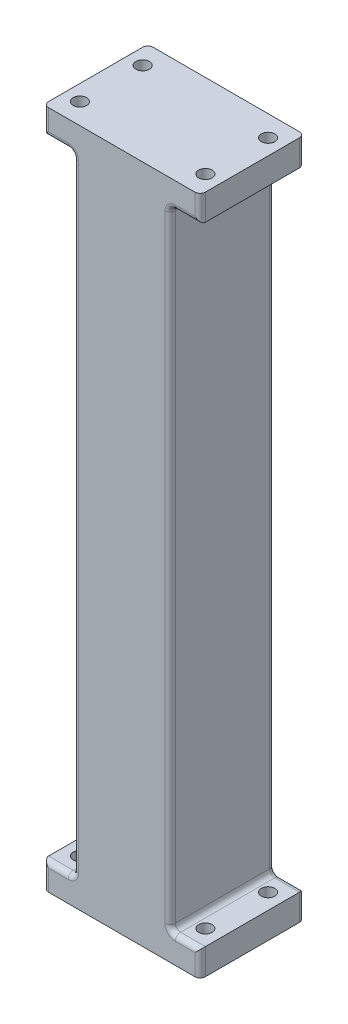
SolidWorks part; units mm, degrees
material "ABS"
ref_plane "Front Plane" through (0, 0, 0) normal (0, 0, 1) x (1, 0, 0)
ref_plane "Top Plane" through (0, 0, 0) normal (0, 1, 0) x (1, 0, 0)
ref_plane "Right Plane" through (0, 0, 0) normal (1, 0, 0) x (0, 0, -1)
sketch "Sketch1" plane through (0, 0, 0) normal (0, 1, 0) x (1, 0, 0)
  line L0 (-40, 0) -> (40, 0) construction
  line L1 (0, -40) -> (0, 40) construction
  line L2 (12, -6) -> (12, 6) construction
  line L3 (-12, -6) -> (12, -6) construction
  line L4 (-12, -6) -> (-12, 6) construction
  line L5 (-12, 6) -> (12, 6) construction
  line L7 (-15, -10) -> (15, -10)
  line L8 (-15, -10) -> (-15, 10)
  line L9 (-15, 10) -> (15, 10)
  line L10 (15, -10) -> (15, 10)
  line L11 (-15, -10) -> (15, 10) construction
  line L12 (-15, 10) -> (15, -10) construction
  circle A0 centre (0, 0) radius 8 construction
  circle A13 centre (-12, 6) radius 1.3
  circle A14 centre (12, 6) radius 1.3
  circle A15 centre (12, -6) radius 1.3
  circle A16 centre (-12, -6) radius 1.3
  circle A17 centre (0, 8) radius 1 construction
  circle A18 centre (5.6569, 5.6569) radius 1 construction
  circle A19 centre (8, 0) radius 1 construction
  circle A20 centre (5.6569, -5.6569) radius 1 construction
  circle A21 centre (0, -8) radius 1 construction
  circle A22 centre (-5.6569, -5.6569) radius 1 construction
  circle A23 centre (-8, 0) radius 1 construction
  circle A24 centre (-5.6569, 5.6569) radius 1 construction
  point P3 (0, 0)
  point P6 (0, 0)
  point P26 (0, 0)
  point P28 (12, 0)
  point P31 (0, -6)
  point P38 (0, 0)
  dimension "D1" = 16
  dimension "D4" = 2.6
  dimension "D5" = 2
  dimension "D2" = 12
  dimension "D3" = 24
  dimension "D7" = 20
  dimension "D8" = 30
  dimension "D6" = 8
extrude "Boss-Extrude1" add sketch "Sketch1" along normal blind 5
sketch "Sketch2" plane through (0, 5, 0) normal (0, 1, 0) x (1, 0, 0)
  line L0 (15, 10) -> (-15, 10) construction
  line L1 (-9.25, -10) -> (9.25, -10)
  line L2 (-9.25, -10) -> (-9.25, 10)
  line L3 (-9.25, 10) -> (9.25, 10)
  line L4 (9.25, -10) -> (9.25, 10)
  line L5 (-9.25, -10) -> (9.25, 10) construction
  line L6 (-9.25, 10) -> (9.25, -10) construction
  point P0 (0, 0)
  dimension "D1" = 18.5
extrude "Boss-Extrude2" add sketch "Sketch2" along normal blind 120
ref_axis "Axis1" through (9.25, 65, 10) along (-1, 0, 0)
ref_plane "Plane1" through (0, 65, 0) normal (0, 1, 0) x (1, 0, 0)
mirror "Mirror1" about plane through (0, 65, 0) normal (0, 1, 0) of "Boss-Extrude1"
fillet "Fillet1" radius 1 24 edges at (12.125, 5, 10) (12.125, 5, -10) (-12.125, 5, -10) (-12.125, 5, 10) (-12.125, 125, -10) (-12.125, 125, 10) (12.125, 125, 10) (12.125, 125, -10) (9.25, 5, 0) (-9.25, 5, 0) (-9.25, 125, 0) (9.25, 125, 0) (9.25, 65, -10) (9.25, 65, 10) (-9.25, 65, 10) (-9.25, 65, -10) (-15, 2.5, -10) (-15, 2.5, 10) (15, 2.5, 10) (15, 2.5, -10) (15, 127.5, 10) (15, 127.5, -10) (-15, 127.5, -10) (-15, 127.5, 10)
